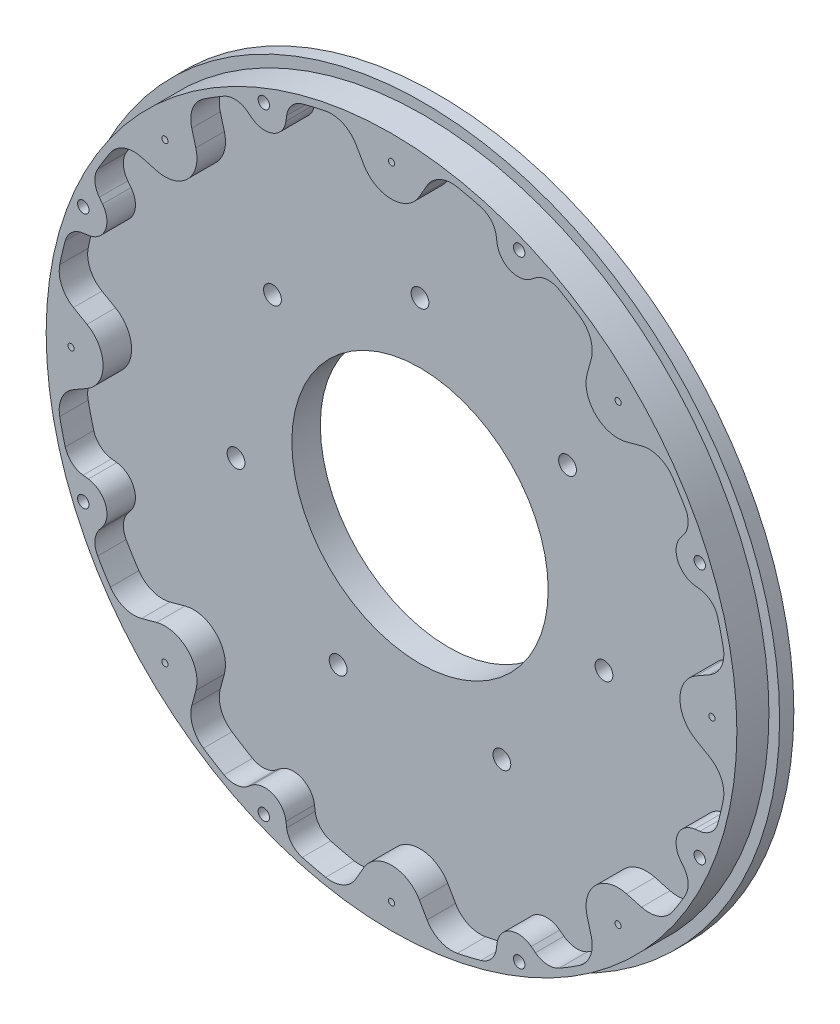
SolidWorks part; units mm, degrees
material "6061 Alloy"
ref_plane "Front Plane" through (0, 0, 0) normal (0, 0, 1) x (1, 0, 0)
ref_plane "Top Plane" through (0, 0, 0) normal (0, 1, 0) x (1, 0, 0)
ref_plane "Right Plane" through (0, 0, 0) normal (1, 0, 0) x (0, 0, -1)
sketch "Sketch1" plane through (0, 0, 0) normal (0, 0, 1) x (1, 0, 0)
  circle A0 centre (0, 0) radius 50
  circle A1 centre (0, 0) radius 48.5
  dimension "D1" = 97
  dimension "D2" = 100
sketch "Sketch2" plane through (0, 0, 0) normal (0, 0, 1) x (1, 0, 0)
  circle A0 centre (0, 0) radius 50
  dimension "D1" = 100
extrude "Boss-Extrude1" add sketch "Sketch2" along normal blind 8
sketch "Sketch3" plane through (0, 0, 0) normal (0, 0, 1) x (1, 0, 0)
  circle A0 centre (0, 0) radius 18
  dimension "D1" = 36
extrude "Cut-Extrude1" cut sketch "Sketch3" along normal through all
sketch "Sketch4" plane through (0, 0, 0) normal (0, 0, 1) x (1, 0, 0)
  line L0 (0, 0) -> (0, 58.7274) construction
  line L1 (4, 41.4126) -> (4, 32.249)
  line L2 (32.1115, 26.4547) -> (25.6319, 19.9751)
  line L3 (41.4126, 4) -> (32.249, 4)
  line L4 (26.4547, 32.1115) -> (19.9751, 25.6319)
  line L5 (41.4126, -4) -> (32.249, -4)
  line L6 (32.1115, -26.4547) -> (25.6319, -19.9751)
  line L7 (26.4547, -32.1115) -> (19.9751, -25.6319)
  line L8 (4, -41.4126) -> (4, -32.249)
  line L9 (-4, -41.4126) -> (-4, -32.249)
  line L10 (-26.4547, -32.1115) -> (-19.9751, -25.6319)
  line L11 (-32.1115, -26.4547) -> (-25.6319, -19.9751)
  line L12 (-41.4126, -4) -> (-32.249, -4)
  line L13 (-41.4126, 4) -> (-32.249, 4)
  line L14 (-32.1115, 26.4547) -> (-25.6319, 19.9751)
  line L15 (-26.4547, 32.1115) -> (-19.9751, 25.6319)
  line L16 (-4, 41.4126) -> (-4, 32.249)
  arc A2 (4, 41.4126) -> (7.5, 44.3706) centre (7, 41.4126) cw
  arc A3 (32.1115, 26.4547) -> (36.6781, 26.0715) centre (34.2328, 24.3334) cw
  arc A4 (41.4126, 4) -> (44.3706, 7.5) centre (41.4126, 7) ccw
  arc A5 (26.4547, 32.1115) -> (26.0715, 36.6781) centre (24.3334, 34.2328) ccw
  arc A6 (44.3706, 7.5) -> (36.6781, 26.0715) centre (0, 0) ccw
  arc A7 (29.3173, 6.3636) -> (25.2302, 16.2307) centre (0, 0) ccw
  arc A8 (32.249, 4) -> (29.3173, 6.3636) centre (32.249, 7) cw
  arc A9 (25.2302, 16.2307) -> (25.6319, 19.9751) centre (27.7533, 17.8538) cw
  arc A10 (41.4126, -4) -> (44.3706, -7.5) centre (41.4126, -7) cw
  arc A11 (32.1115, -26.4547) -> (36.6781, -26.0715) centre (34.2328, -24.3334) ccw
  arc A12 (36.6781, -26.0715) -> (44.3706, -7.5) centre (0, 0) ccw
  arc A13 (25.2302, -16.2307) -> (29.3173, -6.3636) centre (0, 0) ccw
  arc A14 (25.6319, -19.9751) -> (25.2302, -16.2307) centre (27.7533, -17.8538) cw
  arc A15 (29.3173, -6.3636) -> (32.249, -4) centre (32.249, -7) cw
  arc A16 (26.4547, -32.1115) -> (26.0715, -36.6781) centre (24.3334, -34.2328) cw
  arc A17 (4, -41.4126) -> (7.5, -44.3706) centre (7, -41.4126) ccw
  arc A18 (26.0715, 36.6781) -> (7.5, 44.3706) centre (0, 0) ccw
  arc A19 (7.5, -44.3706) -> (26.0715, -36.6781) centre (0, 0) ccw
  arc A20 (6.3636, -29.3173) -> (16.2307, -25.2302) centre (0, 0) ccw
  arc A21 (4, -32.249) -> (6.3636, -29.3173) centre (7, -32.249) cw
  arc A22 (16.2307, -25.2302) -> (19.9751, -25.6319) centre (17.8538, -27.7533) cw
  arc A23 (-4, -41.4126) -> (-7.5, -44.3706) centre (-7, -41.4126) cw
  arc A24 (-26.4547, -32.1115) -> (-26.0715, -36.6781) centre (-24.3334, -34.2328) ccw
  arc A25 (16.2307, 25.2302) -> (6.3636, 29.3173) centre (0, 0) ccw
  arc A26 (19.9751, 25.6319) -> (16.2307, 25.2302) centre (17.8538, 27.7533) cw
  arc A27 (6.3636, 29.3173) -> (4, 32.249) centre (7, 32.249) cw
  arc A29 (-26.0715, -36.6781) -> (-7.5, -44.3706) centre (0, 0) ccw
  arc A30 (-16.2307, -25.2302) -> (-6.3636, -29.3173) centre (0, 0) ccw
  arc A32 (-19.9751, -25.6319) -> (-16.2307, -25.2302) centre (-17.8538, -27.7533) cw
  arc A34 (-6.3636, -29.3173) -> (-4, -32.249) centre (-7, -32.249) cw
  arc A35 (-32.1115, -26.4547) -> (-36.6781, -26.0715) centre (-34.2328, -24.3334) cw
  arc A37 (-41.4126, -4) -> (-44.3706, -7.5) centre (-41.4126, -7) ccw
  arc A39 (-44.3706, -7.5) -> (-36.6781, -26.0715) centre (0, 0) ccw
  arc A40 (-29.3173, -6.3636) -> (-25.2302, -16.2307) centre (0, 0) ccw
  arc A41 (-32.249, -4) -> (-29.3173, -6.3636) centre (-32.249, -7) cw
  arc A42 (-25.2302, -16.2307) -> (-25.6319, -19.9751) centre (-27.7533, -17.8538) cw
  arc A43 (-41.4126, 4) -> (-44.3706, 7.5) centre (-41.4126, 7) cw
  arc A44 (-32.1115, 26.4547) -> (-36.6781, 26.0715) centre (-34.2328, 24.3334) ccw
  arc A45 (-36.6781, 26.0715) -> (-44.3706, 7.5) centre (0, 0) ccw
  arc A46 (-25.2302, 16.2307) -> (-29.3173, 6.3636) centre (0, 0) ccw
  arc A47 (-25.6319, 19.9751) -> (-25.2302, 16.2307) centre (-27.7533, 17.8538) cw
  arc A48 (-29.3173, 6.3636) -> (-32.249, 4) centre (-32.249, 7) cw
  arc A49 (-26.4547, 32.1115) -> (-26.0715, 36.6781) centre (-24.3334, 34.2328) cw
  arc A50 (-4, 41.4126) -> (-7.5, 44.3706) centre (-7, 41.4126) ccw
  arc A51 (-7.5, 44.3706) -> (-26.0715, 36.6781) centre (0, 0) ccw
  arc A52 (-6.3636, 29.3173) -> (-16.2307, 25.2302) centre (0, 0) ccw
  arc A53 (-4, 32.249) -> (-6.3636, 29.3173) centre (-7, 32.249) cw
  arc A54 (-16.2307, 25.2302) -> (-19.9751, 25.6319) centre (-17.8538, 27.7533) cw
  point P72 (0, 0)
  point P131 (0, 0)
  dimension "D1" = 8
  dimension "D2" = 45
  dimension "D4" = 3
  dimension "D6" = 3
  dimension "D5" = 30
  dimension "D3" = 4
sketch "Sketch5" plane through (0, 0, 0) normal (0, 0, 1) x (1, 0, 0)
  circle A0 centre (0, 0) radius 30
  circle A1 centre (0, 0) radius 50
  dimension "D1" = 100
  dimension "D2" = 60
extrude "Cut-Extrude2" cut sketch "Sketch5" along normal blind 1.5 from surface starting at face at (18, 0, 0)
extrude "Cut-Extrude3" cut sketch "Sketch4" along normal blind 1.5 from surface starting at face at (50, 0, 1.5)
sketch "Sketch18" plane through (0, 0, 0) normal (0, 0, 1) x (1, 0, 0)
  circle A0 centre (0, 0) radius 18
  circle A1 centre (0, 0) radius 31
  dimension "D1" = 36
  dimension "D2" = 62
extrude "Cut-Extrude10" cut sketch "Sketch18" against normal blind 4 from surface starting at face at (18, 0, 8)
sketch "Sketch7" plane through (0, 0, 0) normal (0, 0, 1) x (1, 0, 0)
  line L16 (0, 0) -> (0, 51.2761) construction
  line L18 (-3.9038, 42.7616) -> (-4.9916, 44.6588)
  line L19 (3.9038, 42.7616) -> (4.9916, 44.6588)
  line L48 (0, 0) -> (-21.2507, 51.3038) construction
  line L49 (-14.8204, 42.5688) -> (-14.7225, 43.3128)
  line L50 (-19.6211, 40.5803) -> (-20.2164, 41.0371)
  line L51 (14.8204, 42.5688) -> (14.7225, 43.3128)
  line L52 (19.6211, 40.5803) -> (20.2164, 41.0371)
  line L53 (32.9974, 27.4766) -> (35.1082, 28.0489)
  line L54 (27.4766, 32.9974) -> (28.0489, 35.1082)
  line L55 (40.5803, 19.6211) -> (41.0371, 20.2164)
  line L56 (42.5688, 14.8204) -> (43.3128, 14.7225)
  line L57 (42.7616, -3.9038) -> (44.6588, -4.9916)
  line L58 (42.7616, 3.9038) -> (44.6588, 4.9916)
  line L59 (42.5688, -14.8204) -> (43.3128, -14.7225)
  line L60 (40.5803, -19.6211) -> (41.0371, -20.2164)
  line L61 (27.4766, -32.9974) -> (28.0489, -35.1082)
  line L62 (32.9974, -27.4766) -> (35.1082, -28.0489)
  line L63 (19.6211, -40.5803) -> (20.2164, -41.0371)
  line L64 (14.8204, -42.5688) -> (14.7225, -43.3128)
  line L65 (-3.9038, -42.7616) -> (-4.9916, -44.6588)
  line L66 (3.9038, -42.7616) -> (4.9916, -44.6588)
  line L67 (-14.8204, -42.5688) -> (-14.7225, -43.3128)
  line L68 (-19.6211, -40.5803) -> (-20.2164, -41.0371)
  line L69 (-32.9974, -27.4766) -> (-35.1082, -28.0489)
  line L70 (-27.4766, -32.9974) -> (-28.0489, -35.1082)
  line L71 (-40.5803, -19.6211) -> (-41.0371, -20.2164)
  line L72 (-42.5688, -14.8204) -> (-43.3128, -14.7225)
  line L73 (-42.7616, 3.9038) -> (-44.6588, 4.9916)
  line L74 (-42.7616, -3.9038) -> (-44.6588, -4.9916)
  line L75 (-42.5688, 14.8204) -> (-43.3128, 14.7225)
  line L76 (-40.5803, 19.6211) -> (-41.0371, 20.2164)
  line L77 (-27.4766, 32.9974) -> (-28.0489, 35.1082)
  line L78 (-32.9974, 27.4766) -> (-35.1082, 28.0489)
  circle A0 centre (0, 0) radius 45 construction
  arc A2 (-3.9038, 42.7616) -> (3.9038, 42.7616) centre (0, 45) ccw
  arc A69 (-4.9916, 44.6588) -> (-9.2397, 46.5927) centre (-8.4617, 42.6691) ccw
  arc A72 (4.9916, 44.6588) -> (9.2397, 46.5927) centre (8.4617, 42.6691) cw
  arc A123 (-9.2397, 46.5927) -> (-12.5402, 45.8148) centre (0, 0) ccw
  arc A124 (-39.4795, 26.4125) -> (-41.2632, 23.5287) centre (0, 0) ccw
  arc A125 (-46.5927, -9.2397) -> (-45.8148, -12.5402) centre (0, 0) ccw
  arc A126 (-26.4125, -39.4795) -> (-23.5287, -41.2632) centre (0, 0) ccw
  arc A127 (9.2397, -46.5927) -> (12.5402, -45.8148) centre (0, 0) ccw
  arc A128 (39.4795, -26.4125) -> (41.2632, -23.5287) centre (0, 0) ccw
  arc A129 (46.5927, 9.2397) -> (45.8148, 12.5402) centre (0, 0) ccw
  arc A130 (26.4125, 39.4795) -> (23.5287, 41.2632) centre (0, 0) ccw
  circle A131 centre (0, 0) radius 46.5 construction
  arc A132 (-19.6211, 40.5803) -> (-14.8204, 42.5688) centre (-17.7948, 42.9604) ccw
  arc A133 (-23.5287, 41.2632) -> (-26.4125, 39.4795) centre (0, 0) ccw
  arc A134 (-20.2164, 41.0371) -> (-23.5287, 41.2632) centre (-22.0427, 38.6571) ccw
  arc A135 (-14.7225, 43.3128) -> (-12.5402, 45.8148) centre (-11.7482, 42.9212) cw
  arc A136 (14.8204, 42.5688) -> (19.6211, 40.5803) centre (17.7948, 42.9604) ccw
  arc A137 (14.7225, 43.3128) -> (12.5402, 45.8148) centre (11.7482, 42.9212) ccw
  arc A138 (20.2164, 41.0371) -> (23.5287, 41.2632) centre (22.0427, 38.6571) cw
  arc A139 (27.4766, 32.9974) -> (32.9974, 27.4766) centre (31.8198, 31.8198) ccw
  arc A140 (35.1082, 28.0489) -> (39.4795, 26.4125) centre (36.1549, 24.1883) cw
  arc A141 (28.0489, 35.1082) -> (26.4125, 39.4795) centre (24.1883, 36.1549) ccw
  arc A142 (40.5803, 19.6211) -> (42.5688, 14.8204) centre (42.9604, 17.7948) ccw
  arc A143 (41.0371, 20.2164) -> (41.2632, 23.5287) centre (38.6571, 22.0427) ccw
  arc A144 (43.3128, 14.7225) -> (45.8148, 12.5402) centre (42.9212, 11.7482) cw
  arc A145 (42.7616, 3.9038) -> (42.7616, -3.9038) centre (45, 0) ccw
  arc A146 (44.6588, -4.9916) -> (46.5927, -9.2397) centre (42.6691, -8.4617) cw
  arc A147 (44.6588, 4.9916) -> (46.5927, 9.2397) centre (42.6691, 8.4617) ccw
  arc A148 (42.5688, -14.8204) -> (40.5803, -19.6211) centre (42.9604, -17.7948) ccw
  arc A149 (43.3128, -14.7225) -> (45.8148, -12.5402) centre (42.9212, -11.7482) ccw
  arc A150 (41.0371, -20.2164) -> (41.2632, -23.5287) centre (38.6571, -22.0427) cw
  arc A151 (32.9974, -27.4766) -> (27.4766, -32.9974) centre (31.8198, -31.8198) ccw
  arc A152 (28.0489, -35.1082) -> (26.4125, -39.4795) centre (24.1883, -36.1549) cw
  arc A153 (35.1082, -28.0489) -> (39.4795, -26.4125) centre (36.1549, -24.1883) ccw
  arc A154 (19.6211, -40.5803) -> (14.8204, -42.5688) centre (17.7948, -42.9604) ccw
  arc A155 (20.2164, -41.0371) -> (23.5287, -41.2632) centre (22.0427, -38.6571) ccw
  arc A156 (14.7225, -43.3128) -> (12.5402, -45.8148) centre (11.7482, -42.9212) cw
  arc A157 (3.9038, -42.7616) -> (-3.9038, -42.7616) centre (0, -45) ccw
  arc A158 (-4.9916, -44.6588) -> (-9.2397, -46.5927) centre (-8.4617, -42.6691) cw
  arc A159 (4.9916, -44.6588) -> (9.2397, -46.5927) centre (8.4617, -42.6691) ccw
  arc A160 (-14.8204, -42.5688) -> (-19.6211, -40.5803) centre (-17.7948, -42.9604) ccw
  arc A161 (-14.7225, -43.3128) -> (-12.5402, -45.8148) centre (-11.7482, -42.9212) ccw
  arc A162 (-20.2164, -41.0371) -> (-23.5287, -41.2632) centre (-22.0427, -38.6571) cw
  arc A163 (-27.4766, -32.9974) -> (-32.9974, -27.4766) centre (-31.8198, -31.8198) ccw
  arc A164 (-35.1082, -28.0489) -> (-39.4795, -26.4125) centre (-36.1549, -24.1883) cw
  arc A165 (-28.0489, -35.1082) -> (-26.4125, -39.4795) centre (-24.1883, -36.1549) ccw
  arc A166 (-40.5803, -19.6211) -> (-42.5688, -14.8204) centre (-42.9604, -17.7948) ccw
  arc A167 (-41.0371, -20.2164) -> (-41.2632, -23.5287) centre (-38.6571, -22.0427) ccw
  arc A168 (-43.3128, -14.7225) -> (-45.8148, -12.5402) centre (-42.9212, -11.7482) cw
  arc A169 (-42.7616, -3.9038) -> (-42.7616, 3.9038) centre (-45, 0) ccw
  arc A170 (-44.6588, 4.9916) -> (-46.5927, 9.2397) centre (-42.6691, 8.4617) cw
  arc A171 (-44.6588, -4.9916) -> (-46.5927, -9.2397) centre (-42.6691, -8.4617) ccw
  arc A172 (-42.5688, 14.8204) -> (-40.5803, 19.6211) centre (-42.9604, 17.7948) ccw
  arc A173 (-43.3128, 14.7225) -> (-45.8148, 12.5402) centre (-42.9212, 11.7482) ccw
  arc A174 (-41.0371, 20.2164) -> (-41.2632, 23.5287) centre (-38.6571, 22.0427) cw
  arc A175 (-32.9974, 27.4766) -> (-27.4766, 32.9974) centre (-31.8198, 31.8198) ccw
  arc A176 (-28.0489, 35.1082) -> (-26.4125, 39.4795) centre (-24.1883, 36.1549) cw
  arc A177 (-35.1082, 28.0489) -> (-39.4795, 26.4125) centre (-36.1549, 24.1883) ccw
  arc A178 (12.5402, 45.8148) -> (9.2397, 46.5927) centre (0, 0) ccw
  arc A179 (41.2632, 23.5287) -> (39.4795, 26.4125) centre (0, 0) ccw
  arc A180 (23.5287, -41.2632) -> (26.4125, -39.4795) centre (0, 0) ccw
  arc A181 (-12.5402, -45.8148) -> (-9.2397, -46.5927) centre (0, 0) ccw
  arc A182 (-45.8148, 12.5402) -> (-46.5927, 9.2397) centre (0, 0) ccw
  arc A183 (45.8148, -12.5402) -> (46.5927, -9.2397) centre (0, 0) ccw
  arc A184 (-41.2632, -23.5287) -> (-39.4795, -26.4125) centre (0, 0) ccw
  circle A185 centre (0, 0) radius 31
  point P73 (0, 0)
  point P77 (0, 0)
  point P82 (0, 0)
  point P171 (0, 0)
  dimension "D1" = 90
  dimension "D2" = 8
  dimension "D3" = 9
  dimension "D4" = 62
  dimension "D5" = 4
  dimension "D6" = 95
  dimension "D7" = 93
  dimension "D9" = 6
  dimension "D10" = 3
  dimension "D8" = 22.5
extrude "Cut-Extrude9" cut sketch "Sketch7" against normal blind 4 from surface starting at face at (31, 0, 8)
sketch "Sketch6" plane through (0, 0, 0) normal (0, 0, 1) x (1, 0, 0)
  circle A0 centre (0, 0) radius 26.5 construction
  circle A1 centre (0, 26.5) radius 1.5
  circle A2 centre (20.7185, 16.5225) radius 1.5
  circle A3 centre (25.8356, -5.8968) radius 1.5
  circle A4 centre (11.4979, -23.8757) radius 1.5
  circle A5 centre (-11.4979, -23.8757) radius 1.5
  circle A6 centre (-25.8356, -5.8968) radius 1.5
  circle A7 centre (-20.7185, 16.5225) radius 1.5
  point P22 (0, 0)
  dimension "D1" = 53
  dimension "D2" = 3
  dimension "D3" = 7
sketch "Sketch17" plane through (0, 0, 0) normal (0, 0, 1) x (1, 0, 0)
  line L0 (0, 0) -> (0, 45) construction
  line L1 (0, 0) -> (-19.3085, 46.6149) construction
  circle A0 centre (0, 0) radius 45 construction
  circle A1 centre (0, 45) radius 2.5
  circle A2 centre (0, 0) radius 46.85 construction
  circle A3 centre (-17.9287, 43.2838) radius 1
  circle A4 centre (31.8198, 31.8198) radius 2.5
  circle A5 centre (45, 0) radius 2.5
  circle A6 centre (31.8198, -31.8198) radius 2.5
  circle A7 centre (0, -45) radius 2.5
  circle A8 centre (-31.8198, -31.8198) radius 2.5
  circle A9 centre (-45, 0) radius 2.5
  circle A10 centre (-31.8198, 31.8198) radius 2.5
  circle A11 centre (17.9287, 43.2838) radius 1
  circle A12 centre (43.2838, 17.9287) radius 1
  circle A13 centre (43.2838, -17.9287) radius 1
  circle A14 centre (17.9287, -43.2838) radius 1
  circle A15 centre (-17.9287, -43.2838) radius 1
  circle A16 centre (-43.2838, -17.9287) radius 1
  circle A17 centre (-43.2838, 17.9287) radius 1
  point P26 (0, 0)
  point P40 (0, 0)
  dimension "D1" = 90
  dimension "D2" = 5
  dimension "D3" = 93.7
  dimension "D4" = 2
  dimension "D5" = 22.5
  dimension "D6" = 8
  dimension "D7" = 8
extrude "Cut-Extrude12" cut sketch "Sketch1" against normal blind 4.5 from surface starting at face at (0, 0, 8)
hole_wizard "M3 Tapped Hole1" positions "Sketch19" profile "Sketch21" tap size "M3" standard "ISO" end condition through all
sketch "Sketch19" plane through (0, 0, 4) normal (0, 0, 1) x (1, 0, 0)
  point P0 (-20.7185, 16.5225)
  point P3 (0, 26.5)
  point P6 (20.7185, 16.5225)
  point P9 (25.8356, -5.8968)
  point P12 (11.4979, -23.8757)
  point P15 (-11.4979, -23.8757)
  point P18 (-25.8356, -5.8968)
sketch "Sketch21" plane through (-20.7185, 16.5225, 4) normal (1, 0, 0) x (0, -1, 0)
  line L0 (0, 0) -> (0, 4)
  line L1 (0, 4) -> (1.25, 4)
  line L2 (1.25, 4) -> (1.25, 0)
  line L5 (1.25, 0) -> (0, 0)
  line L11 (0, -6.35) -> (0, 107.95) construction
  dimension "Thru Tap Drill Dia." = 2.5
  dimension "Thru Tap Drill Depth" = 4
cosmetic thread "Hole Thread1" parameters "D2"=3
cosmetic thread "Hole Thread2" parameters "D2"=3
cosmetic thread "Hole Thread3" parameters "D2"=3
cosmetic thread "Hole Thread4" parameters "D2"=3
cosmetic thread "Hole Thread5" parameters "D2"=3
cosmetic thread "Hole Thread6" parameters "D2"=3
cosmetic thread "Hole Thread7" parameters "D2"=3
hole_wizard "M2 Tapped Hole1" positions "Sketch22" profile "Sketch23" tap size "M2" standard "ISO"
sketch "Sketch22" plane through (0, 0, 8) normal (0, 0, 1) x (1, 0, 0)
  point P0 (-17.9287, 43.2838)
  point P3 (-43.2838, 17.9287)
  point P6 (-43.2838, -17.9287)
  point P9 (-17.9287, -43.2838)
  point P12 (17.9287, -43.2838)
  point P15 (43.2838, -17.9287)
  point P18 (43.2838, 17.9287)
  point P21 (17.9287, 43.2838)
cosmetic thread "Hole Thread8" parameters "D1"=6, "D2"=2
cosmetic thread "Hole Thread9" parameters "D1"=6, "D2"=2
cosmetic thread "Hole Thread10" parameters "D1"=6, "D2"=2
cosmetic thread "Hole Thread11" parameters "D1"=6, "D2"=2
cosmetic thread "Hole Thread12" parameters "D1"=6, "D2"=2
cosmetic thread "Hole Thread13" parameters "D1"=6, "D2"=2
cosmetic thread "Hole Thread14" parameters "D1"=6, "D2"=2
cosmetic thread "Hole Thread15" parameters "D1"=6, "D2"=2
sketch "Sketch23" plane through (-17.9287, 43.2838, 8) normal (1, 0, 0) x (0, -1, 0)
  line L0 (0, 0) -> (0, 5.9807)
  line L1 (0, 5.9807) -> (0.8, 5.5)
  line L2 (0.8, 5.5) -> (0.8, 0)
  line L5 (0.8, 0) -> (0, 0)
  line L10 (0, 5.9807) -> (-0.8, 5.5) construction
  line L11 (0, -6.35) -> (0, 107.95) construction
  dimension "Tap Drill Dia." = 1.6
  dimension "Tap Drill Depth" = 5.5
  dimension "Drill Angle" = 118
hole_wizard "M5 Tapped Hole1" positions "Sketch24" profile "Sketch25" tap size "M5" standard "ISO"
sketch "Sketch24" plane through (0, 0, 1.5) normal (0, 0, -1) x (-1, 0, 0)
  point P0 (0, 45)
  point P3 (-31.8198, 31.8198)
  point P6 (-45, 0)
  point P9 (-31.8198, -31.8198)
  point P12 (0, -45)
  point P15 (31.8198, -31.8198)
  point P18 (45, 0)
  point P21 (31.8198, 31.8198)
sketch "Sketch25" plane through (0, 45, 1.5) normal (1, 0, 0) x (0, 1, 0)
  line L0 (0, 0) -> (0, 6.7618)
  line L1 (0, 6.7618) -> (2.1, 5.5)
  line L2 (2.1, 5.5) -> (2.1, 0)
  line L5 (2.1, 0) -> (0, 0)
  line L10 (0, 6.7618) -> (-2.1, 5.5) construction
  line L11 (0, -6.35) -> (0, 107.95) construction
  dimension "Tap Drill Dia." = 4.2
  dimension "Tap Drill Depth" = 5.5
  dimension "Drill Angle" = 118
cosmetic thread "Hole Thread16" parameters "D1"=10, "D2"=5
cosmetic thread "Hole Thread17" parameters "D1"=10, "D2"=5
cosmetic thread "Hole Thread18" parameters "D1"=10, "D2"=5
cosmetic thread "Hole Thread19" parameters "D1"=10, "D2"=5
cosmetic thread "Hole Thread20" parameters "D1"=10, "D2"=5
cosmetic thread "Hole Thread21" parameters "D1"=10, "D2"=5
cosmetic thread "Hole Thread22" parameters "D1"=10, "D2"=5
cosmetic thread "Hole Thread23" parameters "D1"=10, "D2"=5
